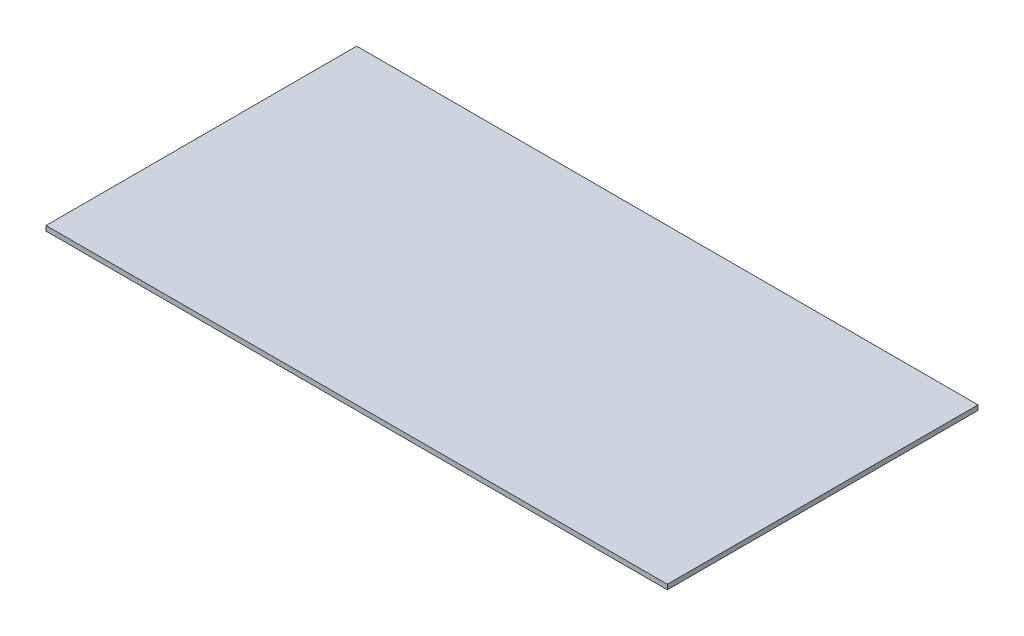
SolidWorks part; units mm, degrees
ref_plane "Front Plane" through (0, 0, 0) normal (0, 0, 1) x (1, 0, 0)
ref_plane "Top Plane" through (0, 0, 0) normal (0, 1, 0) x (1, 0, 0)
ref_plane "Right Plane" through (0, 0, 0) normal (1, 0, 0) x (0, 0, -1)
sketch "Sketch2" plane through (0, 0, 0) normal (0, 1, 0) x (1, 0, 0)
  line L1 (-1219.2, 609.6) -> (1219.2, 609.6)
  line L2 (-1219.2, 609.6) -> (-1219.2, -609.6)
  line L3 (-1219.2, -609.6) -> (1219.2, -609.6)
  line L4 (1219.2, 609.6) -> (1219.2, -609.6)
  line L5 (-1219.2, 609.6) -> (1219.2, -609.6) construction
  line L6 (-1219.2, -609.6) -> (1219.2, 609.6) construction
  point P0 (0, 0)
  dimension "D1" = 2438.4
  dimension "D2" = 1219.2
extrude "Boss-Extrude1" add sketch "Sketch2" along normal blind 9.525 and the other way blind 9.525
